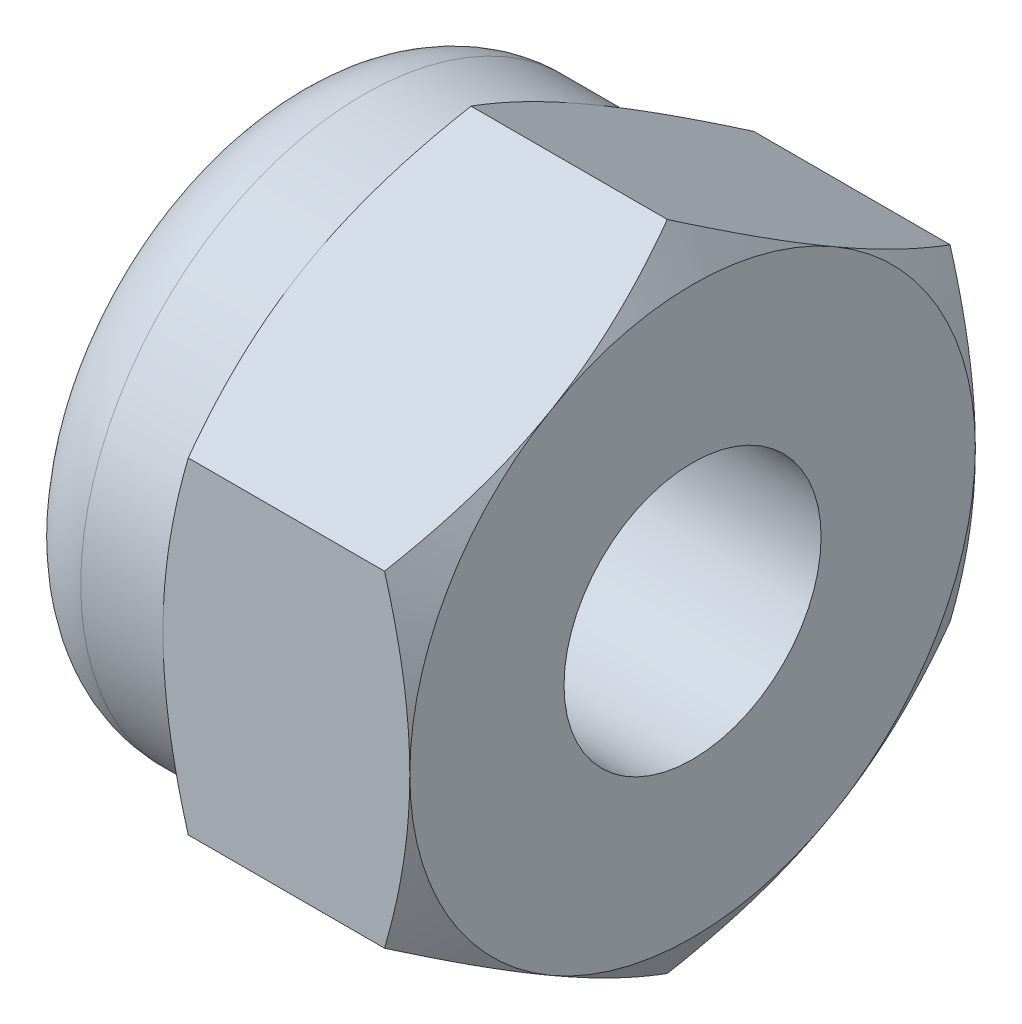
SolidWorks part; units mm, degrees
material "AISI 1020"
ref_plane "XY (Front)" through (0, 0, 0) normal (0, 0, 1) x (1, 0, 0)
ref_plane "XZ (Top)" through (0, 0, 0) normal (0, 1, 0) x (1, 0, 0)
ref_plane "YZ (Right)" through (0, 0, 0) normal (1, 0, 0) x (0, 0, -1)
ref_axis "X" through (-88.99, 0, 0) along (1, 0, 0)
ref_axis "Y" through (0, 55, 0) along (0, -1, 0)
ref_axis "Z" through (0, 0, -88.99) along (0, 0, 1)
sketch "Sketch1" plane through (0, 0, 0) normal (1, 0, 0) x (0, 0, -1)
  line L1 (0, 3.1754) -> (-2.75, 1.5877)
  line L2 (-2.75, 1.5877) -> (-2.75, -1.5877)
  line L3 (-2.75, -1.5877) -> (0, -3.1754)
  line L4 (0, -3.1754) -> (2.75, -1.5877)
  line L5 (2.75, -1.5877) -> (2.75, 1.5877)
  line L6 (2.75, 1.5877) -> (0, 3.1754)
  circle A0 centre (0, 0) radius 2.75 construction
  dimension "s" = 5.5
extrude "Boss-Extrude1" add sketch "Sketch1" against normal blind 4
sketch "Sketch2" plane through (0, 0, 0) normal (0, 0, 1) x (1, 0, 0)
  line L0 (-8.122, 0) -> (-4, 0) construction
  line L1 (-4, 1.5877) -> (-4, -1.5877) construction
  line L2 (0, 2.75) -> (-0.2456, 3.1754)
  line L3 (0, 3.1754) -> (0, 1.5877) construction
  line L4 (-4, 3.1754) -> (0, 3.1754) construction
  line L5 (-0.2456, 3.1754) -> (0, 3.1754)
  line L6 (0, 3.1754) -> (0, 2.75)
  line L7 (0, -2.75) -> (0, 2.75) construction
  line L8 (-4, 3.1754) -> (-4, 1.5877) construction
  line L9 (-2.1544, 3.1754) -> (-2.4, 2.75)
  line L10 (-4, 0) -> (-4, 1.25)
  line L12 (-2.4, 2.75) -> (-3.2, 2.75)
  line L13 (-4, 1.95) -> (-4.4254, 1.95)
  line L14 (-4, 1.25) -> (0, 1.25)
  line L15 (0, 1.5877) -> (0, -1.5877) construction
  line L16 (0, 1.25) -> (0, 0)
  line L17 (0, 0) -> (-4, 0)
  line L18 (-4.4254, 1.95) -> (-4.4254, 3.1754)
  line L20 (-4.4254, 3.1754) -> (-2.1544, 3.1754)
  line L21 (-2.4, 2.75) -> (0, 2.75) construction
  line L22 (-2.4, 2.75) -> (-2.4, 3.1754) construction
  line L23 (-1.2, 2.75) -> (-1.2, 3.1754) construction
  arc A0 (-3.2, 2.75) -> (-4, 1.95) centre (-3.2, 1.95) ccw
  dimension "D1" = 30
  dimension "R" = 0.8
  dimension "m" = 2.4
  dimension "M_t" = 2.5
revolve "Cut-Revolve4" cut sketch "Sketch2" angle 360 about L0
cosmetic thread "Cosmetic Thread1" parameters "D2"=3
